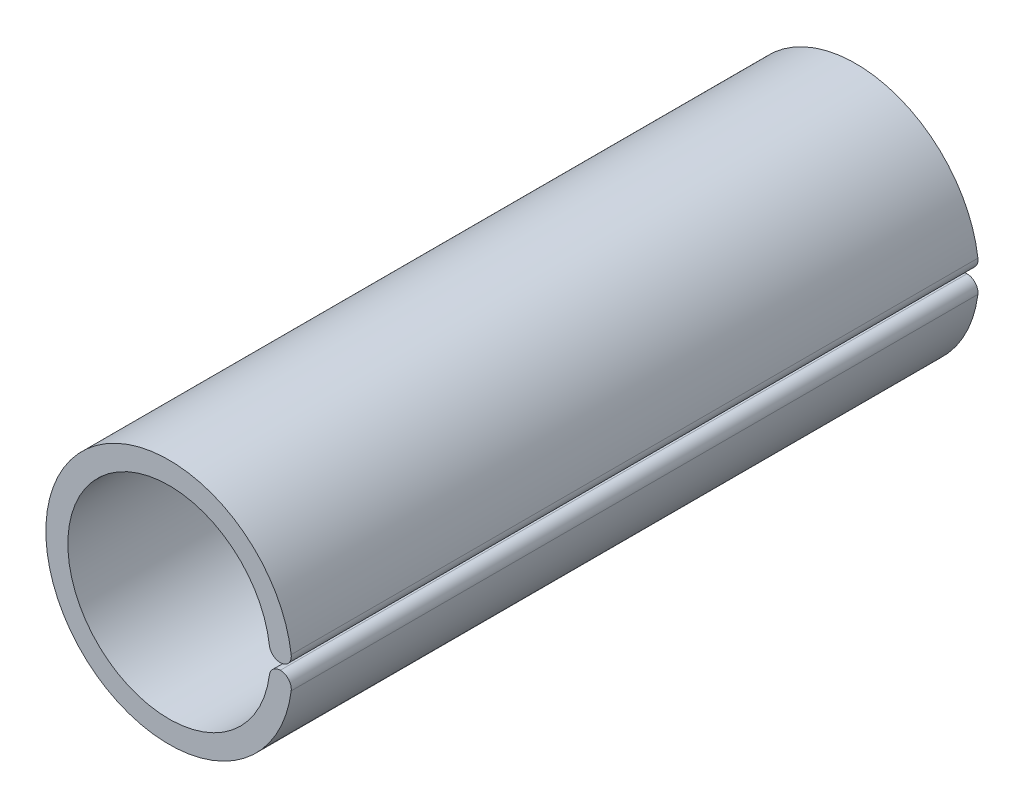
SolidWorks part; units mm, degrees
ref_plane "정면" through (0, 0, 0) normal (0, 0, 1) x (1, 0, 0)
ref_plane "윗면" through (0, 0, 0) normal (0, 1, 0) x (1, 0, 0)
ref_plane "우측면" through (0, 0, 0) normal (1, 0, 0) x (0, 0, -1)
sketch "스케치1" plane through (0, 0, 0) normal (0, 0, 1) x (1, 0, 0)
  circle A0 centre (0, 0) radius 4.6
  circle A1 centre (0, 0) radius 5.6
  dimension "D1" = 9.2
  dimension "D2" = 1
extrude "보스-돌출1" add sketch "스케치1" along normal blind 31.22
sketch "스케치2" plane through (0, 0, 0) normal (0, 0, 1) x (1, 0, 0)
  line L1 (3.1261, 0.15) -> (7.2125, 0.15)
  line L2 (3.1261, 0.15) -> (3.1261, -0.15)
  line L3 (3.1261, -0.15) -> (7.2125, -0.15)
  line L4 (7.2125, 0.15) -> (7.2125, -0.15)
  point P4 (3.1261, 0)
  dimension "D1" = 0.3
extrude "컷-돌출1" cut sketch "스케치2" along normal through all
fillet "필렛1" radius 0.5 4 edges at (4.5976, -0.15, 15.61) (5.598, -0.15, 15.61) (5.598, 0.15, 15.61) (4.5976, 0.15, 15.61)
